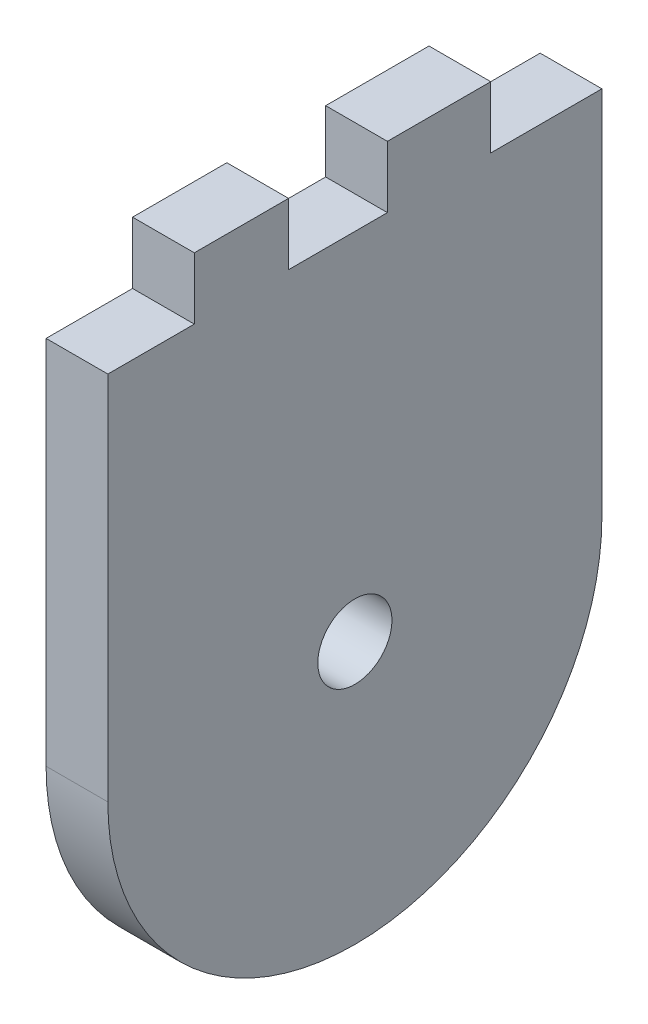
SolidWorks part; units mm, degrees
material "ABS"
ref_plane "Płaszczyzna przednia" through (0, 0, 0) normal (0, 0, 1) x (1, 0, 0)
ref_plane "Płaszczyzna górna" through (0, 0, 0) normal (0, 1, 0) x (1, 0, 0)
ref_plane "Płaszczyzna prawa" through (0, 0, 0) normal (1, 0, 0) x (0, 0, -1)
sketch "Szkic1" plane through (0, 0, 0) normal (0, 0, 1) x (1, 0, 0)
  line L0 (0, 0) -> (-5, 0)
  line L1 (-5, 55) -> (0, 55)
  line L2 (0, 0) -> (0, 51.5)
  line L4 (0, 51.5) -> (0, 55)
  line L5 (-5, 0) -> (-5, 55)
  dimension "D3" = 5
  dimension "D4" = 55
extrude "Dodanie-wyciągnięcie1" add sketch "Szkic1" along normal blind 40
fillet "Zaokrąglenie1" radius 20 2 edges at (-2.5, 0, 0) (-2.5, 0, 40)
ref_plane "Płaszczyzna1" through (0, 47, 0) normal (0, 1, 0) x (1, 0, 0)
sketch "Szkic6" plane through (-5, 0, 0) normal (-1, 0, 0) x (0, 0, 1)
  line L1 (20, 55) -> (20, 0) construction
  line L2 (40, 55) -> (0, 55) construction
  circle A1 centre (20, 21.2376) radius 3
  dimension "D1" = 6
extrude "Wytnij-wyciągnięcie1" cut sketch "Szkic6" against normal blind 10
sketch "Szkic8" plane through (-5, 0, 0) normal (-1, 0, 0) x (0, 0, 1)
  line L0 (0, 50) -> (9, 50)
  line L1 (0, 55) -> (0, 20) construction
  line L2 (9, 50) -> (9, 55)
  line L3 (40, 55) -> (0, 55) construction
  line L4 (9, 55) -> (17.366, 55)
  line L5 (17.366, 55) -> (17.366, 50)
  line L6 (17.366, 50) -> (25.366, 50)
  line L7 (25.366, 50) -> (25.366, 55)
  line L8 (25.366, 55) -> (33, 55)
  line L9 (33, 55) -> (33, 50)
  line L10 (33, 50) -> (40, 50)
  line L11 (40, 55) -> (40, 20) construction
  line L12 (40, 50) -> (40, 57.0743)
  line L13 (40, 57.0743) -> (0, 57.0743)
  line L14 (0, 57.0743) -> (0, 50)
  point P8 (9, 52.5)
  point P17 (4.5, 50)
  dimension "D1" = 9
  dimension "D2" = 5
  dimension "D3" = 8
  dimension "D4" = 7
extrude "Wytnij-wyciągnięcie2" cut sketch "Szkic8" against normal through all
